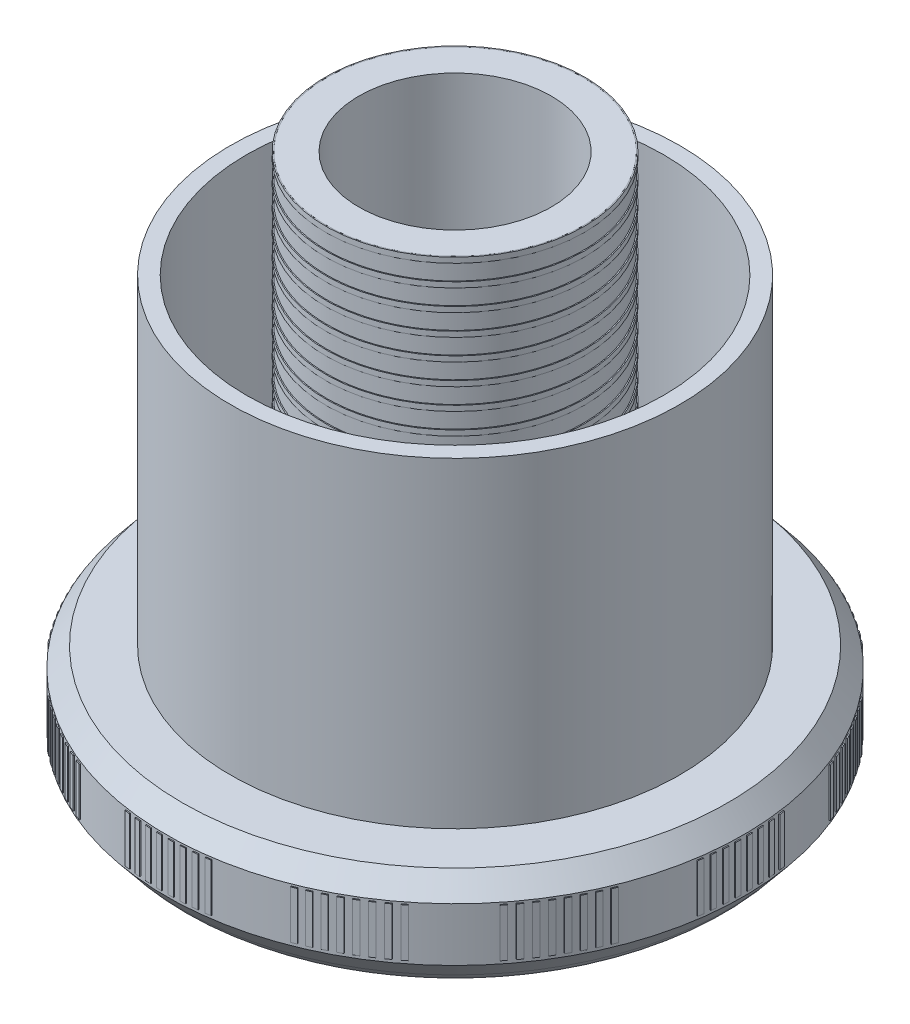
SolidWorks part; units mm, degrees
other "Objet de détail2"
material "PE haute densité"
ref_plane "Plan de face" through (0, 0, 0) normal (0, 0, 1) x (1, 0, 0)
ref_plane "Plan de dessus" through (0, 0, 0) normal (0, 1, 0) x (1, 0, 0)
ref_plane "Plan de droite" through (0, 0, 0) normal (1, 0, 0) x (0, 0, -1)
sketch "Esquisse1" plane through (0, 0, 0) normal (0, 0, 1) x (1, 0, 0)
  line L0 (0, 0) -> (-5, 0)
  line L1 (-5, 0) -> (-5, 2)
  line L2 (-5, 2) -> (-9, 2)
  line L3 (-9, 2) -> (-9, -2)
  line L4 (-9, -2) -> (-21, -2)
  line L5 (-21, -2) -> (-21, 2)
  line L6 (-21, 2) -> (-23, 2)
  line L7 (-23, 2) -> (-23, -2)
  line L8 (-27, 1.1708) -> (-27, 6.1708)
  line L9 (-27, 6.1708) -> (-25.5, 8)
  line L10 (-25.5, 8) -> (-21, 8)
  line L11 (-21, 8) -> (-21, 38)
  line L12 (-21, 38) -> (-19.5, 38)
  line L13 (-19.5, 38) -> (-19.5, 8)
  line L14 (-19.5, 8) -> (-12, 8)
  line L15 (-12, 8) -> (-12, 48)
  line L16 (-12, 48) -> (-9, 48)
  line L17 (-9, 48) -> (-9, 8)
  line L18 (-9, 8) -> (0, 8)
  line L19 (0, 8) -> (0, 0)
  line L20 (0, 8) -> (0, 24.8331) construction
  line L21 (-23, -2) -> (-21, -2) construction
  line L22 (-21, 2) -> (-9, 2) construction
  line L23 (-27, 1.1708) -> (-25.5, -0.6583)
  line L24 (-25.5, 8) -> (-25.5, -0.6583) construction
  line L25 (-27, 3.6708) -> (-25.5, 3.6708) construction
  line L26 (-9, 8) -> (-12, 8) construction
  line L27 (-19.5, 8) -> (-21, 8) construction
  arc A0 (-23, -2) -> (-25.5, -0.6583) centre (-23, 1) cw
  point P25 (-10.5, 48)
  dimension "D11" = 3
  dimension "D1" = 50
  dimension "D2" = 54
  dimension "D3" = 10
  dimension "D4" = 10
  dimension "D5" = 2
  dimension "D6" = 4
  dimension "D7" = 18
  dimension "D8" = 42
  dimension "D9" = 46
  dimension "D10" = 5
  dimension "D12" = 4.5
  dimension "D13" = 42
  dimension "D14" = 1.5
  dimension "D15" = 3
  dimension "D16" = 40
revolve "Révolution1" add sketch "Esquisse1" angle 360 about L20
sketch "Esquisse2" plane through (0, 48, 0) normal (0, 1, 0) x (1, 0, 0)
  circle A0 centre (0, 0) radius 12 construction
  circle A1 centre (0, 0) radius 12
extrude "Extru.-Mince1" add sketch "Esquisse2" against normal blind 0.5 separate body thin thin type one direction wall 0.1
ref_axis "Axe1" through (0, 0, 0) along (0, 1, 0)
pattern_linear "Répétition linéaire1" count 19 spacing 2 along (0, -1, 0) of "Extru.-Mince1"
sketch "Esquisse3" plane through (0, 0, 0) normal (0, 1, 0) x (1, 0, 0)
  line L0 (-4, 26.8737) -> (4, 26.8737) construction
  line L1 (0, 26.8737) -> (0, 0) construction
  line L2 (0, 0) -> (-4, 26.8737) construction
  line L3 (0, 0) -> (-3.4945, 26.8737) construction
  line L4 (-3.4945, 26.8737) -> (-3.9897, 26.8047) construction
  line L5 (-3.7421, 26.8392) -> (0, 0) construction
  line L6 (-3.975, 26.7058) -> (-3.9897, 26.8047)
  line L7 (-3.9897, 26.8047) -> (-3.4945, 26.8737)
  line L8 (-3.4945, 26.8737) -> (-3.4816, 26.7746)
  line L9 (-3.4816, 26.7746) -> (-3.975, 26.7058)
  circle A0 centre (0, 0) radius 27 construction
  circle A1 centre (0, 0) radius 27 construction
  dimension "D2" = 0.1
  dimension "D1" = 8
  dimension "D3" = 0.5
extrude "Boss.-Extru.1" add sketch "Esquisse3" along normal blind 4.5 from offset 1.5
pattern_circular "Répétition circulaire1" count 8 every 2.3 about axis through (0, 6.1708, 0) along (0, -1, 0) of "Boss.-Extru.1"
pattern_circular "Répétition circulaire2" count 12 over 360 about axis through (0, 8, 0) along (0, -1, 0) of "Boss.-Extru.1", "Répétition circulaire1" reverse direction yes
equation "\"Cout_variable\"= int((\"Masse\" * \"Prix_au_kg\" + \"Prix_unitaire\" + \"Prix_m2\" * \"SW-Superficie\" / 1000000 + \"Prix_m3\" * \"SW-Volume\" /1000000)*100)/100"
equation "\"Cout_horaire\"= int((\"Taux_horaire_brut\" * \"Temps_fabrication\"  +  IIF ( \"Estimation_bois\" = 1 , \"SW-Volume\" * 350 /1000000,0))*100)/100"
